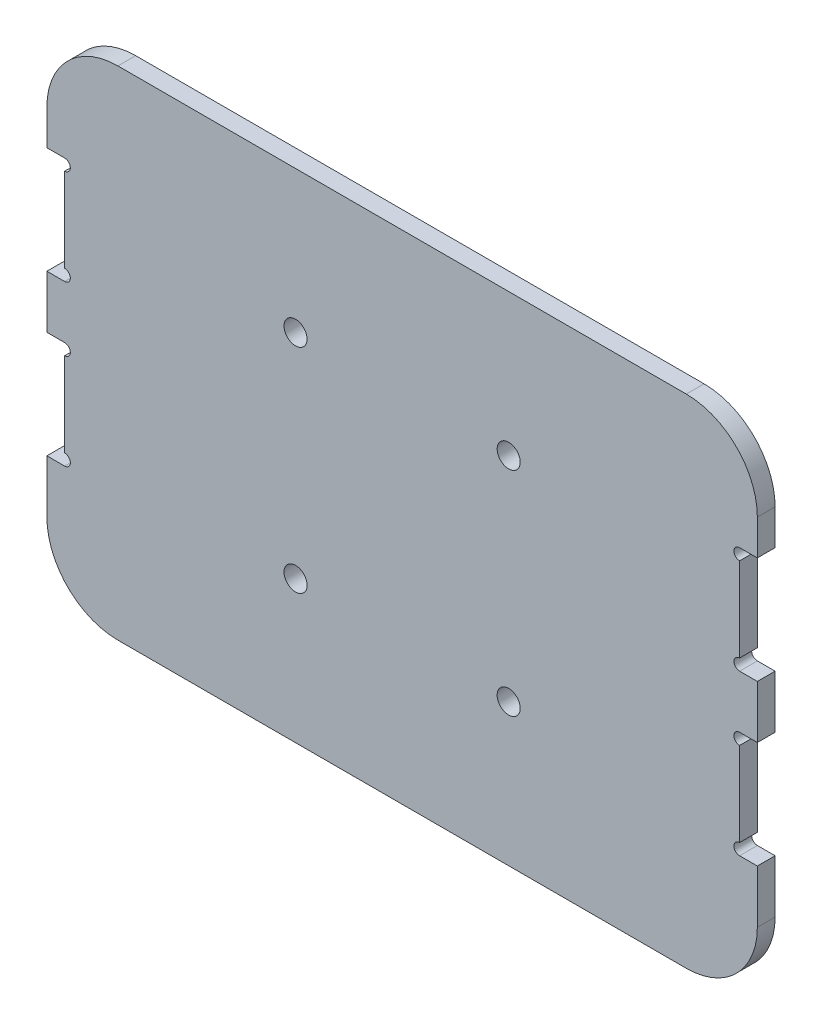
SolidWorks part; units mm, degrees
material "Hexcel AS4C (3000 丝)"
ref_plane "前视基准面" through (0, 0, 0) normal (0, 0, 1) x (1, 0, 0)
ref_plane "上视基准面" through (0, 0, 0) normal (0, 1, 0) x (1, 0, 0)
ref_plane "右视基准面" through (0, 0, 0) normal (1, 0, 0) x (0, 0, -1)
other "Configuration Table"
sketch "草图1" plane through (0, 0, 0) normal (0, 0, 1) x (1, 0, 0)
  line L0 (0, 0) -> (284.1069, 0) construction
  line L1 (-100, 120) -> (100, 120)
  line L2 (-100, 120) -> (-100, -20)
  line L3 (-100, -20) -> (100, -20)
  line L4 (100, 120) -> (100, -20)
  line L5 (0, 0) -> (0, 194.938) construction
  circle A0 centre (30, 80) radius 3.25
  circle A1 centre (30, 20) radius 3.25
  circle A2 centre (-30, 80) radius 3.25
  circle A3 centre (-30, 20) radius 3.25
  dimension "D3" = 6.5
  dimension "D6" = 40
  dimension "D1" = 120
  dimension "D2" = 200
  dimension "D4" = 30
  dimension "D5" = 60
  dimension "D7" = 20
extrude "凸台-拉伸1" add sketch "草图1" along normal blind 5 contours L4 L3 L2 L1 | A1 | A3 | A2 | A0
fillet "圆角1" radius 20 4 edges at (-100, 120, 2.5) (-100, -20, 2.5) (100, -20, 2.5) (100, 120, 2.5)
sketch "草图3" plane through (0, 0, 5) normal (0, 0, 1) x (1, 0, 0)
  line L0 (0, 126.8429) -> (0, -134.2378) construction
  line L1 (-131.0539, 0) -> (117.702, 0) construction
  line L2 (100, 100) -> (100, 0) construction
  line L3 (95, 90) -> (100, 90)
  line L4 (95, 90) -> (95, 60)
  line L5 (95, 60) -> (100, 60)
  line L6 (100, 90) -> (100, 60)
  line L8 (95, 45) -> (100, 45)
  line L9 (95, 45) -> (95, 15)
  line L10 (95, 15) -> (100, 15)
  line L11 (100, 45) -> (100, 15)
  line L26 (-100, 45) -> (-100, 15)
  line L27 (-95, 15) -> (-100, 15)
  line L28 (-95, 45) -> (-95, 15)
  line L29 (-95, 45) -> (-100, 45)
  line L31 (-100, 90) -> (-100, 60)
  line L32 (-95, 60) -> (-100, 60)
  line L33 (-95, 90) -> (-95, 60)
  line L34 (-95, 90) -> (-100, 90)
  dimension "D1" = 5
  dimension "D2" = 5
  dimension "D3" = 15
  dimension "D4" = 30
  dimension "D5" = 15
  dimension "D6" = 30
extrude "切除-拉伸1" cut sketch "草图3" against normal blind 39
sketch "草图4" plane through (0, 0, 5) normal (0, 0, 1) x (1, 0, 0)
  line L0 (95, 90) -> (95, 60) construction
  line L1 (95, 45) -> (95, 15) construction
  line L2 (0, 0) -> (0, 130.3564) construction
  line L3 (100, 90) -> (95, 90) construction
  line L4 (95, 60) -> (100, 60) construction
  line L5 (100, 45) -> (95, 45) construction
  line L6 (95, 15) -> (100, 15) construction
  circle A0 centre (95, 88.45) radius 1.55
  circle A1 centre (95, 61.55) radius 1.55
  circle A2 centre (95, 43.45) radius 1.55
  circle A3 centre (95, 16.55) radius 1.55
  circle A4 centre (-95, 16.55) radius 1.55
  circle A5 centre (-95, 43.45) radius 1.55
  circle A6 centre (-95, 61.55) radius 1.55
  circle A7 centre (-95, 88.45) radius 1.55
  dimension "D1" = 3.1
extrude "切除-拉伸2" cut sketch "草图4" against normal blind 10
other "移动面1" flip direction yes face at (-97.5, 90, 2.5) face at (-94.225, 88.45, 2.5) face at (-94.225, 61.55, 2.5) face at (-97.5, 60, 2.5) face at (-97.5, 45, 2.5) face at (-94.225, 43.45, 2.5) face at (-94.225, 16.55, 2.5) face at (-97.5, 15, 2.5) face at (94.225, 16.55, 2.5) face at (97.5, 15, 2.5) face at (94.225, 43.45, 2.5) face at (97.5, 45, 2.5) face at (97.5, 60, 2.5) face at (94.225, 61.55, 2.5) face at (94.225, 88.45, 2.5) face at (97.5, 90, 2.5) offset 0.05 parameters "D1"=0.05
